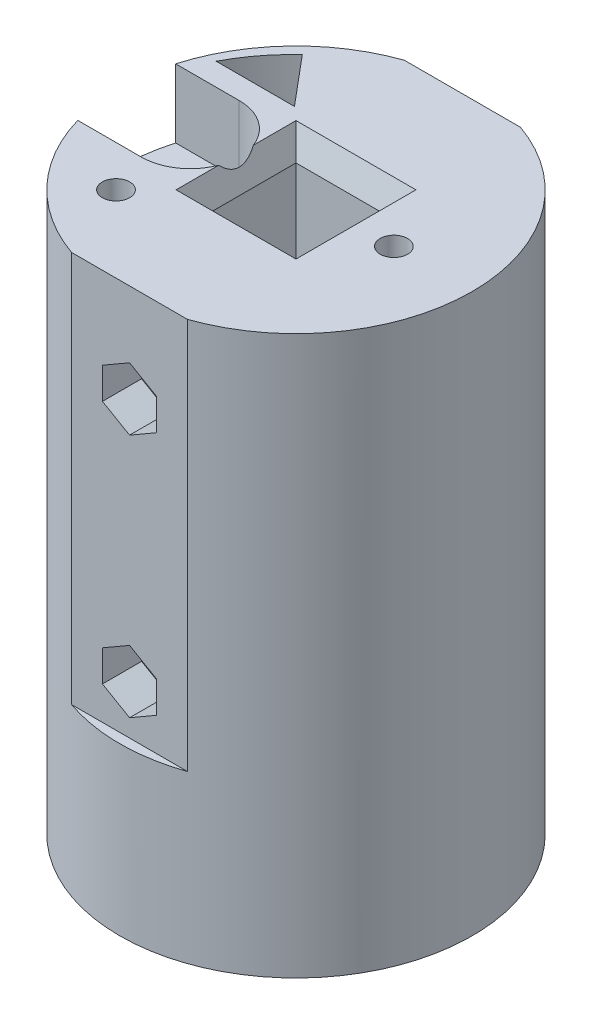
SolidWorks part; units mm, degrees
ref_plane "Спереди" through (0, 0, 0) normal (0, 0, 1) x (1, 0, 0)
ref_plane "Сверху" through (0, 0, 0) normal (0, 1, 0) x (1, 0, 0)
ref_plane "Справа" through (0, 0, 0) normal (1, 0, 0) x (0, 0, -1)
sketch "Sketch1" plane through (0, 0, 0) normal (0, 1, 0) x (1, 0, 0)
  line L0 (-5.125, 0) -> (-18, 0) construction
  line L1 (5.125, -5.125) -> (-5.125, -5.125)
  line L2 (5.125, -5.125) -> (5.125, 5.125)
  line L3 (5.125, 5.125) -> (-5.125, 5.125)
  line L4 (-5.125, -5.125) -> (-5.125, 5.125)
  line L5 (5.125, -5.125) -> (-5.125, 5.125) construction
  line L6 (5.125, 5.125) -> (-5.125, -5.125) construction
  circle A0 centre (0, 0) radius 18
  circle A1 centre (-12, 0) radius 2
  dimension "D1" = 36
  dimension "D3" = 6
  dimension "D2" = 10.25
extrude "Boss-Extrude1" add sketch "Sketch1" along normal blind 57
sketch "Sketch2" plane through (0, 57, 0) normal (0, 1, 0) x (1, 0, 0)
  line L0 (-10.8, 5) -> (-17.2916, 5)
  line L1 (-10.8, -5) -> (-17.2916, -5)
  line L2 (-5.125, 0) -> (-18, 0) construction
  line L3 (-5.125, 5.125) -> (-5.125, -5.125) construction
  circle A1 centre (0, 0) radius 18 construction
  arc A2 (-17.2916, 5) -> (-17.2916, -5) centre (0, 0) ccw
  arc A3 (-10.8, 5) -> (-10.8, -5) centre (-10.8, 0) cw
  point P12 (-5.8, 0)
  dimension "D1" = 5
extrude "Cut-Extrude1" cut sketch "Sketch2" against normal blind 7
sketch "Sketch4" plane through (0, 0, 0) normal (0, -1, 0) x (-1, 0, 0)
  line L0 (0, 0) -> (18, 21.4516) construction
  line L1 (0, 0) -> (18, -21.4516) construction
  line L2 (18, 21.4516) -> (18, -21.4516) construction
  line L3 (0, 0) -> (13.6996, 11.6756) construction
  line L4 (0, 0) -> (13.6996, -11.6756) construction
  line L5 (0, 0) -> (18, 0) construction
  line L6 (5.125, 5.125) -> (5.125, -5.125) construction
  line L7 (11.5702, 13.7888) -> (5.1423, 6.1284) construction
  line L8 (5.1423, 6.1284) -> (5.1423, -4.3826) construction
  line L9 (5.1423, -4.3826) -> (13.6996, -11.6756) construction
  line L10 (5.1423, 0.8729) -> (18.1354, 0.8729) construction
  line L12 (15.8104, 5.5479) -> (6.4604, 5.5479)
  line L13 (15.8104, 5.5479) -> (15.8104, -3.8021)
  line L14 (15.8104, -3.8021) -> (6.4604, -3.8021)
  line L15 (6.4604, 5.5479) -> (6.4604, -3.8021)
  line L16 (15.8104, 5.5479) -> (6.4604, -3.8021) construction
  line L17 (15.8104, -3.8021) -> (6.4604, 5.5479) construction
  arc A0 (13.6996, -11.6756) -> (11.5702, 13.7888) centre (0.5154, 0.0431) ccw construction
  circle A2 centre (0, 0) radius 18 construction
  point P2 (11, 0)
  point P5 (11.5702, 13.7888)
  point P7 (4.1157, 3.5076)
  point P8 (11.5702, -13.7888)
  point P11 (5.125, -6.1077)
  point P16 (11.1354, 0.8729)
  dimension "D5" = 10
  dimension "D1" = 100
  dimension "D2" = 3
  dimension "D3" = 3
  dimension "D4" = 9.35
  dimension "D6" = 7
extrude "Cut-Extrude3" cut sketch "Sketch4" against normal blind 20.4
sketch "Sketch5" plane through (0, 57, 0) normal (0, 1, 0) x (1, 0, 0)
  line L0 (0, 18) -> (0, -18) construction
  line L1 (5.9161, 17) -> (-5.9161, 17)
  line L2 (5.9161, -17) -> (-5.9161, -17)
  circle A0 centre (0, 0) radius 18 construction
  arc A1 (5.9161, 17) -> (-5.9161, 17) centre (0, 0) ccw
  arc A2 (5.9161, -17) -> (-5.9161, -17) centre (0, 0) cw
  point P11 (0, 17)
  dimension "D1" = 1
extrude "Cut-Extrude4" cut sketch "Sketch5" against normal blind 40
sketch "Sketch6" plane through (0, 0, -17) normal (0, 0, -1) x (-1, 0, 0)
  line L0 (0, 57) -> (0, 0) construction
  line L1 (5.9161, 57) -> (-5.9161, 57) construction
  line L2 (5.9161, 17) -> (-5.9161, 17) construction
  line L3 (5.9161, 0) -> (-5.9161, 0) construction
  circle A0 centre (0, 47) radius 1.5
  circle A1 centre (0, 22) radius 1.5
  dimension "D1" = 3
  dimension "D2" = 10
  dimension "D3" = 5
extrude "Cut-Extrude5" cut sketch "Sketch6" against normal through all
sketch "Sketch7" plane through (0, 0, -17) normal (0, 0, -1) x (-1, 0, 0)
  circle A0 centre (0, 47) radius 3
  circle A1 centre (0, 22) radius 3
  dimension "D1" = 6
extrude "Cut-Extrude6" cut sketch "Sketch7" against normal blind 3
sketch "Sketch8" plane through (0, 0, 17) normal (0, 0, 1) x (1, 0, 0)
  line L0 (5.9161, 17) -> (5.9161, 57) construction
  line L1 (0, 43.8) -> (2.7713, 45.4)
  line L2 (2.7713, 45.4) -> (2.7713, 48.6)
  line L3 (2.7713, 48.6) -> (0, 50.2)
  line L4 (0, 50.2) -> (-2.7713, 48.6)
  line L5 (-2.7713, 48.6) -> (-2.7713, 45.4)
  line L6 (-2.7713, 45.4) -> (0, 43.8)
  line L9 (0, 18.8) -> (2.7713, 20.4)
  line L10 (2.7713, 20.4) -> (2.7713, 23.6)
  line L11 (2.7713, 23.6) -> (0, 25.2)
  line L12 (0, 25.2) -> (-2.7713, 23.6)
  line L13 (-2.7713, 23.6) -> (-2.7713, 20.4)
  line L14 (-2.7713, 20.4) -> (0, 18.8)
  circle A0 centre (0, 47) radius 3.2 construction
  circle A1 centre (0, 22) radius 3.2 construction
  dimension "D1" = 6.4
extrude "Cut-Extrude7" cut sketch "Sketch8" against normal blind 4
chamfer "Chamfer1" distance 1 angle 70 4 edges at (-5.125, 57, 0) (0, 57, -5.125) (0, 57, 5.125) (5.125, 57, 0) first distance on face at (-5.2523, 57, 0)
sketch "Sketch9" plane through (0, 0, 0) normal (0, -1, 0) x (1, 0, 0)
  line L0 (16.4542, -7.2979) -> (-16.4542, -7.2979) construction
  line L1 (-15.8104, -5.5479) -> (-6.4604, -5.5479) construction
  line L2 (-7.4542, -7.2979) -> (-15.4542, -7.2979)
  line L3 (-7.4542, -7.2979) -> (-11.6323, -12.2772)
  line L4 (5.125, -5.125) -> (-5.125, -5.125) construction
  circle A0 centre (0, 0) radius 18 construction
  arc A1 (-15.4542, -7.2979) -> (-11.6323, -12.2772) centre (0.5168, 1.0043) ccw
  point P10 (-11.4542, -7.2979)
  dimension "D8" = 18
  dimension "D1" = 1.75
  dimension "D2" = 5
  dimension "D3" = 6.5
  dimension "D4" = 50
  dimension "D5" = 8
  dimension "D6" = 2.1729
  dimension "D7" = 23.9084
extrude "Cut-Extrude8" cut sketch "Sketch9" against normal through all
sketch "Sketch12" plane through (0, 57, 0) normal (0, 1, 0) x (1, 0, 0)
  line L0 (18, 0) -> (-10.8, 0) construction
  line L1 (0, 0) -> (-12.7279, -12.7279) construction
  arc A0 (5.9161, -17) -> (5.9161, 17) centre (0, 0) ccw construction
  arc A1 (-17.2916, -5) -> (-5.9161, -17) centre (0, 0) ccw construction
  circle A2 centre (10, 0) radius 1.4
  circle A3 centre (-9.1924, -9.1924) radius 1.4
  dimension "D1" = 2.8
  dimension "D2" = 10
  dimension "D3" = 13
extrude "Cut-Extrude10" cut sketch "Sketch12" against normal blind 20
